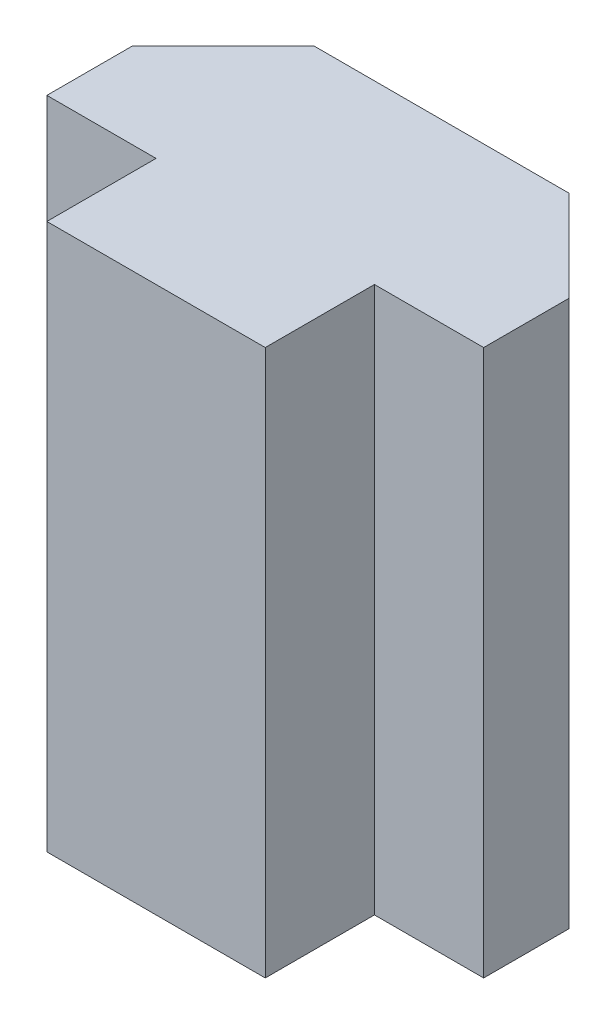
SolidWorks part; units mm, degrees
ref_plane "Front Plane" through (0, 0, 0) normal (0, 0, 1) x (1, 0, 0)
ref_plane "Top Plane" through (0, 0, 0) normal (0, 1, 0) x (1, 0, 0)
ref_plane "Right Plane" through (0, 0, 0) normal (1, 0, 0) x (0, 0, -1)
sketch "Sketch1" plane through (0, 0, 0) normal (0, 1, 0) x (1, 0, 0)
  line L0 (-4.2479, 4.7026) -> (8.7521, 4.7026)
  line L1 (8.7521, 4.7026) -> (8.7521, 1.7026)
  line L2 (-4.2479, 4.7026) -> (-4.2479, 1.7026)
  line L3 (-4.2479, 1.7026) -> (-2.5453, 0)
  line L4 (-44.2539, 0) -> (44.2539, 0) construction
  line L5 (8.7521, 1.7026) -> (7.0495, 0)
  line L6 (-2.5453, 0) -> (7.0495, 0)
  dimension "D1" = 13
  dimension "D2" = 3
  dimension "D3" = 3
extrude "Boss-Extrude1" add sketch "Sketch1" along normal blind 40
sketch "Sketch2" plane through (0, 0, 0) normal (0, 0, 1) x (1, 0, 0)
  line L0 (-2.5453, 40) -> (7.0495, 40) construction
  line L1 (2.2521, 40) -> (5.7521, 40)
  line L2 (2.2521, 40) -> (2.2521, 0)
  line L3 (2.2521, 0) -> (5.7521, 0)
  line L4 (5.7521, 40) -> (5.7521, 0)
  line L5 (55, 0) -> (-55, 0) construction
  line L7 (2.2521, 40) -> (-1.2479, 40)
  line L8 (2.2521, 40) -> (2.2521, 0)
  line L9 (2.2521, 0) -> (-1.2479, 0)
  line L10 (-1.2479, 40) -> (-1.2479, 0)
  line M9 (-2.5453, 0) -> (7.0495, 0)
  line M11 (7.0495, 40) -> (-2.5453, 40)
  dimension "D1" = 3.5
  dimension "D2" = 3.5
extrude "Boss-Extrude2" add sketch "Sketch2" along normal blind 5 contours L4 L2 M11 M9 | L10 L2 M11 M9 region at (4.0021, 20, 0) region at (0.5021, 20, 0)
sketch "Sketch4" plane through (0, 0, 5) normal (0, 0, 1) x (1, 0, 0)
  line L0 (2.2521, 40) -> (2.2521, 30)
  line L1 (5.7521, 40) -> (-1.2479, 40) construction
  line L2 (2.2521, 0) -> (2.2521, 10)
  line L3 (55, 0) -> (-55, 0) construction
  circle A0 centre (2.2521, 30) radius 2
  circle A1 centre (2.2521, 10) radius 2
  dimension "D3" = 4
  dimension "D4" = 4
  dimension "D1" = 10
  dimension "D2" = 10
extrude "Cut-Extrude1" cut sketch "Sketch4" against normal blind 7 contours A0 | A1 region at (0.8779, 28.6258, 5) region at (3.6263, 8.6258, 5)
sketch "Sketch5" plane through (0, 0, -4.7026) normal (0, 0, -1) x (-1, 0, 0)
  line L0 (-2.2521, 40) -> (-2.2521, 30)
  line L1 (-8.7521, 40) -> (4.2479, 40) construction
  line L2 (-2.2521, 0) -> (-2.2521, 10)
  line L3 (55, 0) -> (-55, 0) construction
  circle A0 centre (-2.2521, 30) radius 3.5
  circle A1 centre (-2.2521, 10) radius 3.5
  dimension "D3" = 7
  dimension "D4" = 7
  dimension "D1" = 10
  dimension "D2" = 10
extrude "Cut-Extrude2" cut sketch "Sketch5" against normal blind 3 draft 27 contours A0 | A1 region at (4.657, 27.5951, -4.7026) region at (-0.1528, 7.5951, -4.7026)
sketch "Sketch7" plane through (0, 0, -4.7026) normal (0, 0, -1) x (-1, 0, 0)
  line L0 (-8.7521, 0) -> (4.2479, 0) construction
  line L1 (-5.7521, 6.5) -> (1.2479, 6.5)
  line L2 (-5.7521, 6.5) -> (-5.7521, -6.5)
  line L3 (-5.7521, -6.5) -> (1.2479, -6.5)
  line L4 (1.2479, 6.5) -> (1.2479, -6.5)
  line L5 (-5.7521, 6.5) -> (1.2479, -6.5) construction
  line L6 (-5.7521, -6.5) -> (1.2479, 6.5) construction
  line L7 (-2.2521, 0) -> (-0.2521, 0)
  line L12 (-0.2521, 0) -> (-0.2521, -5)
  line L13 (-0.2521, -5) -> (-4.2521, -5)
  line L14 (-4.2521, -5) -> (-4.2521, 0)
  line L15 (-8.7521, 40) -> (4.2479, 40) construction
  line L16 (-5.7521, 46.5) -> (1.2479, 46.5)
  line L17 (-5.7521, 46.5) -> (-5.7521, 33.5)
  line L18 (-5.7521, 33.5) -> (1.2479, 33.5)
  line L19 (1.2479, 46.5) -> (1.2479, 33.5)
  line L20 (-5.7521, 46.5) -> (1.2479, 33.5) construction
  line L21 (-5.7521, 33.5) -> (1.2479, 46.5) construction
  line L22 (-4.2521, 0) -> (-0.2521, 0)
  line L23 (-0.2521, 40) -> (-0.2521, 45)
  line L24 (-0.2521, 45) -> (-0.2521, 43.2752)
  line L25 (-0.2521, 45) -> (-4.2521, 45)
  line L26 (-4.2521, 45) -> (-4.2521, 40)
  line L27 (-4.2521, 40) -> (-0.2521, 40)
  point P0 (-2.2521, 0)
  point P7 (-2.2521, 0)
  point P14 (-2.2521, 40)
  line M15 (-8.7521, 0) -> (4.2479, 0)
  line M17 (4.2479, 40) -> (-8.7521, 40)
  dimension "D1" = 13
  dimension "D2" = 7
  dimension "D3" = 2
  dimension "D4" = 5
  dimension "D5" = 13
  dimension "D6" = 7
  dimension "D7" = 4
  dimension "D8" = 5
  dimension "D9" = 4
extrude "Boss-Extrude3" add sketch "Sketch7" against normal blind 3 contours L26 L25 L23 L19 L16 L17 M17 | L13 L14 L2 L3 L4 L12 M15 region at (5.0021, -0.0955, -4.7026) region at (2.2521, 46.4045, -4.7026)
sketch "Sketch9" plane through (0, 0, -4.7026) normal (0, 0, -1) x (-1, 0, 0)
  line L0 (55, 0) -> (-55, 0) construction
  line L1 (-8.7521, 40) -> (4.2479, 40)
  line L2 (-8.7521, 40) -> (-8.7521, 0)
  line L3 (-8.7521, 0) -> (4.2479, 0)
  line L4 (4.2479, 40) -> (4.2479, 0)
  line L5 (4.2479, 40) -> (4.2479, 0) construction
extrude "Cut-Extrude4" cut sketch "Sketch9" against normal up to surface (4.7026 mm away) up to face at (6.4008, 20, 0)
sketch "Sketch10" plane through (0, 0, 0) normal (0, 0, -1) x (-1, 0, 0)
  line L0 (-5.7521, 40) -> (1.2479, 0) construction
  line L2 (-9.7521, 40) -> (5.2479, 40)
  line L3 (-9.7521, 40) -> (-9.7521, 0)
  line L4 (-9.7521, 0) -> (5.2479, 0)
  line L5 (5.2479, 40) -> (5.2479, 0)
  line L6 (-9.7521, 40) -> (5.2479, 0) construction
  line L7 (-9.7521, 0) -> (5.2479, 40) construction
  point P4 (-2.2521, 20)
  dimension "D1" = 15
extrude "Boss-Extrude4" add sketch "Sketch10" along normal blind 2.5
sketch "Sketch11" plane through (0, 0, 0) normal (0, 1, 0) x (1, 0, 0)
  line L0 (-5.2479, 2.5) -> (9.7521, 2.5)
  line L1 (9.7521, 2.5) -> (6.9237, 5.3284)
  line L2 (6.9237, 5.3284) -> (-5.2479, 5.3284)
  line L3 (-5.2479, 2.5) -> (-2.4195, 5.3284)
  line M1 (4.2521, 2.5) -> (5.7521, 2.5)
  line M2 (5.7521, 2.5) -> (5.7521, 4.7026)
  line M3 (5.7521, 4.7026) -> (4.2521, 4.7026)
  line M4 (4.2521, 4.7026) -> (4.2521, 2.5)
extrude "Boss-Extrude7" add sketch "Sketch11" along normal up to surface (40 mm away) contours M4 M1 M2 M3 | L3 L0 L1 L2 M4 M3 M2 region at (1.9602, 0, -3.8263) region at (5.0021, 0, -3.6013) up to face at (-0.4979, 40, -3.6013)
sketch "Sketch12" plane through (0, 0, -4.7026) normal (0, 0, -1) x (-1, 0, 0)
  line L0 (55, 0) -> (-55, 0) construction
  line L1 (-5.7521, -6.5) -> (1.2479, -6.5)
  line L2 (-5.7521, -6.5) -> (-5.7521, 0)
  line L3 (-5.7521, 0) -> (1.2479, 0)
  line L4 (1.2479, -6.5) -> (1.2479, 0)
  line L5 (1.2479, 0) -> (1.2479, -6.5) construction
  line L6 (-0.2521, 0) -> (-0.2521, -5) construction
  line L7 (-4.2521, -5) -> (-0.2521, -5)
  line L8 (-4.2521, -5) -> (-4.2521, 0)
  line L9 (-4.2521, 0) -> (-0.2521, 0)
  line L10 (-0.2521, -5) -> (-0.2521, 0)
  line L11 (-6.9237, 40) -> (2.4195, 40) construction
  line L12 (-5.7521, 46.5) -> (1.2479, 46.5)
  line L13 (-5.7521, 46.5) -> (-5.7521, 40)
  line L14 (-5.7521, 40) -> (1.2479, 40)
  line L15 (1.2479, 46.5) -> (1.2479, 40)
  line L16 (1.2479, 46.5) -> (1.2479, 40) construction
  line L17 (-4.2521, 45) -> (-4.2521, 40) construction
  line L18 (-4.2521, 45) -> (-0.2521, 45)
  line L19 (-4.2521, 45) -> (-4.2521, 40)
  line L20 (-4.2521, 40) -> (-0.2521, 40)
  line L21 (-0.2521, 45) -> (-0.2521, 40)
  line M1 (1.2479, -6.5) -> (1.2479, 0)
  line M2 (1.2479, 0) -> (-0.2521, 0)
  line M3 (-0.2521, 0) -> (-0.2521, -5)
  line M4 (-0.2521, -5) -> (-4.2521, -5)
  line M5 (-4.2521, -5) -> (-4.2521, 0)
  line M6 (-4.2521, 0) -> (-5.7521, 0)
  line M7 (-5.7521, 0) -> (-5.7521, -6.5)
  line M8 (-5.7521, -6.5) -> (1.2479, -6.5)
extrude "Boss-Extrude8" add sketch "Sketch12" along normal up to surface (0.6258 mm away) contours L18 L21 L14 L15 L12 L13 L19 | M8 M1 M2 M3 M4 M5 M6 M7 region at (5.6566, -3.25, -4.7026) region at (2.2521, 46.4045, -4.7026) up to face at (2.2521, 20, -5.3284)
sketch "Sketch13" plane through (0, 0, 0) normal (0, 0, 1) x (1, 0, 0)
  circle A0 centre (2.2521, 30) radius 2
  circle A1 centre (2.2521, 10) radius 2
extrude "Cut-Extrude5" cut sketch "Sketch13" against normal blind 10
sketch "Sketch14" plane through (9.7521, 0, 0) normal (1, 0, 0) x (0, 0, -1)
  line L1 (2.5, 40) -> (0, 40)
  line L2 (2.5, 40) -> (2.5, 0)
  line L3 (2.5, 0) -> (0, 0)
  line L4 (0, 40) -> (0, 0)
extrude "Boss-Extrude9" add sketch "Sketch14" along normal blind 0.5
sketch "Sketch15" plane through (-5.2479, 0, 0) normal (-1, 0, 0) x (0, 0, 1)
  line L1 (-2.5, 40) -> (0, 40)
  line L2 (-2.5, 40) -> (-2.5, 0)
  line L3 (-2.5, 0) -> (0, 0)
  line L4 (0, 40) -> (0, 0)
extrude "Boss-Extrude10" add sketch "Sketch15" along normal blind 0.5
sketch "Sketch16" plane through (0, 0, 0) normal (0, -1, 0) x (1, 0, 0)
  line L0 (-3.1851, -4.5628) -> (-3.7508, -5.1285)
  line L1 (-5.2479, -2.5) -> (-2.4195, -5.3284) construction
  line L2 (-4.5147, -3.2332) -> (-5.0804, -3.7989)
  line L3 (9.0189, -3.2332) -> (9.5846, -3.7989)
  line L4 (9.7521, -2.5) -> (6.9237, -5.3284) construction
  line L5 (7.5623, -4.6898) -> (8.128, -5.2555)
  line L6 (0.657, -5.3284) -> (0.657, -6.1284)
  line L7 (-1.2479, -5.3284) -> (5.7521, -5.3284) construction
  line L8 (0.657, -6.1284) -> (0.657, -6.3714)
  line L9 (9.5846, -3.7989) -> (6.6029, -6.7806)
  line L10 (9.5846, -3.7989) -> (11.5999, -1.7836)
  line L11 (10.2521, -2.5) -> (10.2521, -3.1314)
  line L12 (10.2521, -2.5) -> (9.7521, -2.5)
  line L13 (9.7521, -2.5) -> (6.9237, -5.3284)
  line L14 (6.9237, -5.3284) -> (-2.4195, -5.3284)
  line L15 (-2.4195, -5.3284) -> (-5.2479, -2.5)
  line L16 (-5.2479, -2.5) -> (-5.7479, -2.5)
  line L17 (-3.7508, -5.1285) -> (-6.826, -2.0532)
  line L18 (-5.7479, -2.5) -> (-5.7479, -3.1314)
  line L19 (-3.7508, -5.1285) -> (-2.4195, -6.4598)
  line L20 (-2.4195, -6.4598) -> (6.9237, -6.4598)
  line M3 (6.9237, -5.3284) -> (9.7521, -2.5)
  line M4 (9.7521, -2.5) -> (10.2521, -2.5)
  line M12 (-5.7479, -2.5) -> (-5.2479, -2.5)
  line M13 (-5.2479, -2.5) -> (-2.4195, -5.3284)
  dimension "D1" = 0.8
  dimension "D2" = 0.8
  dimension "D3" = 0.8
  dimension "D4" = 0.8
  dimension "D5" = 0.8
extrude "Boss-Extrude11" add sketch "Sketch16" against normal up to surface (40 mm away) contours L11 L3 L10 M4 M3 | L9 L3 L5 M3 | L19 L20 L9 L5 L14 L0 | L17 L0 L2 M13 | L18 L17 L2 M12 M13 region at (2.1886, 0, -5.8151) region at (-4.1327, 0, -4.1808) region at (-5.2163, 0, -3.0863) region at (8.5734, 0, -4.2444) region at (9.7205, 0, -3.0863) up to face at (2.2521, 40, -1.939)
sketch "Sketch17" plane through (0, 0, -5.3284) normal (0, 0, -1) x (-1, 0, 0)
  line L0 (-4.2521, 40) -> (-4.2521, 45) construction
  line L1 (-5.7521, 46.5) -> (1.2479, 46.5)
  line L2 (-5.7521, 46.5) -> (-5.7521, 40)
  line L3 (-5.7521, 40) -> (1.2479, 40)
  line L4 (1.2479, 46.5) -> (1.2479, 40)
  line L5 (-4.2521, 44.9531) -> (-0.2521, 44.9531)
  line L6 (-4.2521, 44.9531) -> (-4.2521, 40)
  line L7 (-4.2521, 40) -> (-0.2521, 40)
  line L8 (-0.2521, 44.9531) -> (-0.2521, 40)
  line L9 (-0.2521, 40) -> (-0.2521, 45) construction
  line L10 (1.2479, -6.5) -> (-5.7521, -6.5) construction
  line L11 (-5.7521, -6.5) -> (1.2479, -6.5)
  line L12 (-5.7521, -6.5) -> (-5.7521, 0)
  line L13 (-5.7521, 0) -> (1.2479, 0)
  line L14 (1.2479, -6.5) -> (1.2479, 0)
  line L15 (55, 0) -> (-55, 0) construction
  line L16 (1.2479, 0) -> (1.2479, -6.5) construction
  line L18 (-4.2521, -5) -> (0, -5)
  line L19 (-4.2521, -5) -> (-4.2521, 0)
  line L20 (-4.2521, 0) -> (0, 0)
  line L21 (0, -5) -> (0, 0)
  line M1 (1.2479, -6.5) -> (1.2479, 0)
  line M2 (1.2479, 0) -> (-0.2521, 0)
  line M4 (-0.2521, -5) -> (-4.2521, -5)
  line M5 (-4.2521, -5) -> (-4.2521, 0)
  line M6 (-4.2521, 0) -> (-5.7521, 0)
  line M7 (-5.7521, 0) -> (-5.7521, -6.5)
  line M8 (-5.7521, -6.5) -> (1.2479, -6.5)
extrude "Boss-Extrude12" add sketch "Sketch17" along normal up to surface (1.1314 mm away) contours L21 L18 M4 M5 M6 M7 M8 M1 M2 | L5 L8 L3 L4 L1 L2 L6 region at (2.2521, 46.4045, -5.3284) region at (5.6566, -3.25, -5.3284) up to face at (2.2521, 20, -6.4598)
sketch "Sketch18" plane through (0, 0, -5.3284) normal (0, 0, 1) x (1, 0, 0)
  circle A0 centre (2.2521, 30) radius 2
  circle A1 centre (2.2521, 10) radius 2
extrude "Cut-Extrude6" cut sketch "Sketch18" against normal blind 10
sketch "Sketch19" plane through (0, 0, -6.4598) normal (0, 0, -1) x (-1, 0, 0)
  circle A0 centre (-2.2521, 30) radius 2
  circle A1 centre (-2.2521, 10) radius 2
  circle A2 centre (-2.2521, 30) radius 3
  circle A3 centre (-2.2521, 10) radius 3
  dimension "D1" = 6
  dimension "D2" = 6
extrude "Cut-Extrude7" cut sketch "Sketch19" against normal blind 3 draft 19 contours A2 | A3
sketch "Sketch20" plane through (-1.2479, 0, 0) normal (-1, 0, 0) x (0, 0, 1)
  line L1 (5, 40) -> (0, 40)
  line L2 (5, 40) -> (5, 0)
  line L3 (5, 0) -> (0, 0)
  line L4 (0, 40) -> (0, 0)
extrude "Boss-Extrude13" add sketch "Sketch20" along normal blind 0.5
sketch "Sketch21" plane through (5.7521, 0, 0) normal (1, 0, 0) x (0, 0, -1)
  line L1 (-5, 40) -> (0, 40)
  line L2 (-5, 40) -> (-5, 0)
  line L3 (-5, 0) -> (0, 0)
  line L4 (0, 40) -> (0, 0)
extrude "Boss-Extrude14" add sketch "Sketch21" along normal blind 0.5
sketch "Sketch22" plane through (0, 0, 5) normal (0, 0, 1) x (1, 0, 0)
  line L0 (4.2521, 40) -> (5.7521, 40) construction
  line L1 (-1.2479, 46.5) -> (5.7521, 46.5)
  line L2 (-1.2479, 46.5) -> (-1.2479, 40)
  line L3 (-1.2479, 40) -> (5.7521, 40)
  line L4 (5.7521, 46.5) -> (5.7521, 40)
  line L5 (6.2521, 40) -> (-1.7479, 40) construction
  line L6 (55, 0) -> (-55, 0) construction
  line L7 (-1.2479, -6.5) -> (6.2521, -6.5)
  line L8 (-1.2479, -6.5) -> (-1.2479, 0)
  line L9 (-1.2479, 0) -> (6.2521, 0)
  line L10 (6.2521, -6.5) -> (6.2521, 0)
  line L11 (6.2521, 0) -> (6.2521, 40) construction
extrude "Cut-Extrude8" cut sketch "Sketch22" against normal blind 20
sketch "Sketch23" plane through (0, 0, 0) normal (0, 0, 1) x (1, 0, 0)
  circle A0 centre (2.2521, 10) radius 2
  circle A1 centre (2.2521, 30) radius 2
extrude "Boss-Extrude15" add sketch "Sketch23" against normal up to surface (6.4598 mm away) up to face at (2.2521, 20, -6.4598)
sketch "Sketch24" plane through (0, 0, -6.4598) normal (0, 0, -1) x (-1, 0, 0)
  circle A0 centre (-2.2521, 30) radius 3
  circle A1 centre (-2.2521, 10) radius 3
extrude "Boss-Extrude16" add sketch "Sketch24" against normal up to surface (11.4598 mm away) up to face at (4.2521, 30, 5)
sketch "Sketch25" plane through (0, 0, 5) normal (0, 0, 1) x (1, 0, 0)
  line L0 (6.2521, 0) -> (6.2521, 20)
  line L3 (55, 0) -> (-55, 0) construction
  line L4 (6.2521, 0) -> (6.2521, 40) construction
  line L5 (6.2521, 20) -> (6.2521, 20.3582)
  line L6 (10.2521, 40) -> (10.2521, 0) construction
  line L7 (10.2521, 20) -> (-5.7479, 20)
  line L8 (10.2521, 20) -> (10.2521, 40)
  line L9 (10.2521, 40) -> (-5.7479, 40)
  line L10 (-5.7479, 20) -> (-5.7479, 40)
  line M2 (6.2521, 0) -> (6.2521, 40)
  line M3 (6.2521, 40) -> (-1.7479, 40)
  line M4 (-1.7479, 40) -> (-1.7479, 0)
  dimension "D1" = 20
extrude "Cut-Extrude9" cut sketch "Sketch25" against normal blind 20 contours L8 L9 L7 M2 | L7 M2 M3 M4 | L10 L7 L9 M4 region at (2.2521, 30, 5) region at (8.2521, 30, 5) region at (-3.7479, 30, 5)
sketch "Sketch26" plane through (0, 0, 5) normal (0, 0, 1) x (1, 0, 0)
  line L0 (55, 0) -> (-55, 0) construction
  line L1 (-1.7479, 20) -> (6.2521, 20)
  line L2 (-1.7479, 20) -> (-1.7479, 0)
  line L3 (-1.7479, 0) -> (6.2521, 0)
  line L4 (6.2521, 20) -> (6.2521, 0)
  line L5 (6.2521, 20) -> (6.2521, 0) construction
extrude "Cut-Extrude10" cut sketch "Sketch26" against normal blind 1
